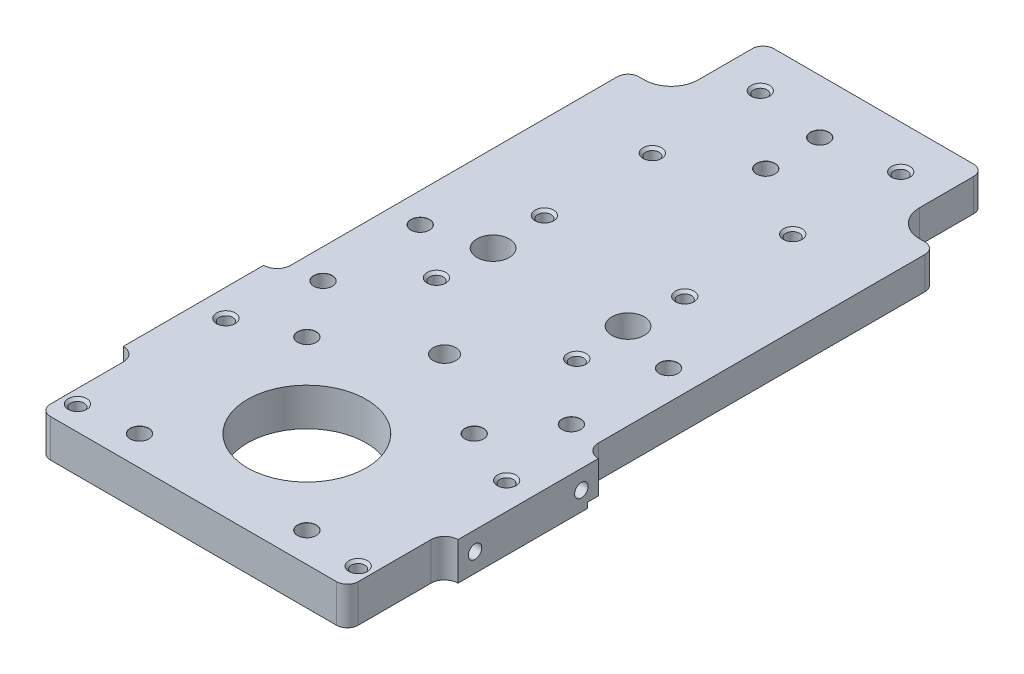
SolidWorks part; units mm, degrees
ref_plane "Top" through (0, 0, 0) normal (0, 0, 1) x (1, 0, 0)
ref_plane "Front" through (0, 0, 0) normal (0, 1, 0) x (1, 0, 0)
ref_plane "Right" through (0, 0, 0) normal (1, 0, 0) x (0, 0, -1)
ref_plane "Left Plane" through (-31, 0, 0) normal (1, 0, 0) x (0, 0, -1)
sketch "Plate Main Sketch" plane through (-158.0855, 0, 24.6791) normal (0, 1, 0) x (-1, 0, 0)
  line L1 (-178.5855, -24.6791) -> (-137.5855, -24.6791)
  line L2 (-127.0855, 57.3209) -> (-127.0855, 83.3209)
  line L3 (-129.5855, 101.3209) -> (-186.5855, 101.3209)
  line L4 (-129.5855, 101.3209) -> (-129.5855, 85.8209)
  line L5 (-158.0855, 101.3209) -> (-158.0855, -24.6791) construction
  line L6 (-178.5855, -12.6791) -> (-178.5855, -24.6791)
  line L7 (-129.5855, 54.8209) -> (-129.5855, -7.6791)
  line L8 (-129.5855, -7.6791) -> (-132.5855, -7.6791)
  line L9 (-137.5855, -12.6791) -> (-137.5855, -24.6791)
  line L10 (-186.5855, -7.6791) -> (-183.5855, -7.6791)
  line L11 (-186.5855, 54.8209) -> (-186.5855, -7.6791)
  line L12 (-189.0855, 57.3209) -> (-189.0855, 83.3209)
  line L13 (-186.5855, 101.3209) -> (-186.5855, 85.8209)
  arc A0 (-129.5855, 85.8209) -> (-127.0855, 83.3209) centre (-127.0855, 85.8209) ccw
  arc A1 (-129.5855, 54.8209) -> (-127.0855, 57.3209) centre (-127.0855, 54.8209) cw
  arc A2 (-132.5855, -7.6791) -> (-137.5855, -12.6791) centre (-132.5855, -12.6791) ccw
  arc A3 (-183.5855, -7.6791) -> (-178.5855, -12.6791) centre (-183.5855, -12.6791) cw
  arc A4 (-186.5855, 54.8209) -> (-189.0855, 57.3209) centre (-189.0855, 54.8209) ccw
  arc A5 (-186.5855, 85.8209) -> (-189.0855, 83.3209) centre (-189.0855, 85.8209) cw
  circle A18 centre (-158.0855, 80.3209) radius 11
  circle A20 centre (-145.5855, 33.3209) radius 3
  circle A21 centre (-170.5855, 33.3209) radius 3
  dimension "D2" = 5
  dimension "D8" = 22
  dimension "D9" = 6
  dimension "D1" = 2.5
  dimension "D3" = 62
  dimension "D4" = 126
  dimension "D5" = 18
  dimension "D6" = 44
  dimension "D15" = 21
  dimension "D17" = 8
  dimension "D7" = 109
  dimension "D10" = 58
  dimension "D11" = 16
extrude "Extrude Plate Main" add sketch "Plate Main Sketch" along normal blind 7
fillet "Corner Fillets" radius 2 6 edges at (-28.5, 3.5, 126) (-28.5, 3.5, 17) (-20.5, 3.5, 0) (20.5, 3.5, 0) (28.5, 3.5, 17) (28.5, 3.5, 126)
sketch "Reccess Sketch" plane through (0, 0, 0) normal (0, 1, 0) x (1, 0, 0)
  line L0 (-8.25, 0) -> (-8.25, -81)
  line L1 (-11.25, -84) -> (-31, -84)
  line L2 (-31, -84) -> (-31, 0)
  line L3 (-31, 0) -> (-8.25, 0)
  line L4 (0, 0) -> (0, -84) construction
  line L5 (31, 0) -> (8.25, 0)
  line L6 (8.25, 0) -> (8.25, -81)
  line L7 (31, -84) -> (31, 0)
  line L8 (11.25, -84) -> (31, -84)
  arc A0 (-8.25, -81) -> (-11.25, -84) centre (-11.25, -81) cw
  arc A1 (8.25, -81) -> (11.25, -84) centre (11.25, -81) ccw
  point P7 (-8.25, -84)
  dimension "D4" = 3
  dimension "D1" = 84
  dimension "D2" = 31
  dimension "D3" = 22.75
hole_wizard "M3x0.5 Tapped Holes" positions "Sketch12" profile "Sketch13" tap size "M3x0.5" standard "ANSI Metric" end condition through all
sketch "Sketch12" plane through (0, 0, 0) normal (0, -1, 0) x (-1, 0, 0)
  line L0 (-13, -8) -> (-13, -68) construction
  line L2 (13, -68) -> (13, -8) construction
  line L4 (26, -121.5) -> (-26, -121.5) construction
  line L5 (-26, -121.5) -> (-26, -94) construction
  line L6 (-26, -94) -> (26, -94) construction
  line L7 (26, -94) -> (26, -121.5) construction
  line L11 (31, -126) -> (-31, -126) construction
  line L12 (31, -126) -> (31, 0) construction
  line L13 (31, 0) -> (-31, 0) construction
  line L14 (-31, -126) -> (-31, 0) construction
  line L15 (0, 0) -> (0, -126) construction
  line L16 (31, -63) -> (-31, -63) construction
  point P0 (-26, -121.5)
  point P2 (-26, -94)
  point P4 (26, -94)
  point P8 (13, -68)
  point P10 (13, -48)
  point P12 (13, -28)
  point P14 (13, -8)
  point P16 (-13, -8)
  point P18 (-13, -28)
  point P20 (-13, -48)
  point P22 (-13, -68)
  point P477 (26, -121.5)
  dimension "D1" = 126
  dimension "D2" = 62
  dimension "D3" = 118
  dimension "D4" = 98
  dimension "D5" = 78
  dimension "D6" = 58
  dimension "D7" = 18
  dimension "D8" = 18
  dimension "D9" = 5
  dimension "D10" = 5
  dimension "D11" = 4.5
  dimension "D12" = 32
sketch "Sketch13" plane through (26, 0, 121.5) normal (1, 0, 0) x (0, 0, -1)
  line L0 (0, 0) -> (0, 7)
  line L1 (0, 7) -> (1.725, 7)
  line L2 (1.25, 6.525) -> (1.25, 0)
  line L5 (1.25, 0) -> (0, 0)
  line L7 (1.725, 7) -> (1.25, 6.525)
  line L8 (-1.725, 7) -> (-1.25, 6.525) construction
  line L11 (0, -6.35) -> (0, 107.95) construction
  dimension "Thru Tap Drill Dia." = 2.5
  dimension "Thru Tap Drill Depth" = 7
  dimension "Far C'Sink Dia." = 3.45
  dimension "Far C'Sink Angle" = 90
cosmetic thread "Hole Thread54" parameters "D2"=3
cosmetic thread "Hole Thread55" parameters "D2"=3
cosmetic thread "Hole Thread56" parameters "D2"=3
cosmetic thread "Hole Thread57" parameters "D2"=3
cosmetic thread "Hole Thread58" parameters "D2"=3
cosmetic thread "Hole Thread59" parameters "D2"=3
cosmetic thread "Hole Thread60" parameters "D2"=3
cosmetic thread "Hole Thread61" parameters "D2"=3
cosmetic thread "Hole Thread62" parameters "D2"=3
cosmetic thread "Hole Thread63" parameters "D2"=3
cosmetic thread "Hole Thread64" parameters "D2"=3
cosmetic thread "Hole Thread65" parameters "D2"=3
hole_wizard "M3 Counter Bores" positions "Sketch4" profile "Sketch5" counterbore size "M3" standard "ANSI Metric" end condition through all
sketch "Sketch4" plane through (0, 0, 0) normal (0, -1, 0) x (-1, 0, 0)
  line L0 (31, -126) -> (-31, -126) construction
  line L1 (-31, -126) -> (-31, 0) construction
  line L2 (-31, 0) -> (31, 0) construction
  line L3 (31, 0) -> (31, -126) construction
  line L5 (15.5, -120.5) -> (-15.5, -120.5) construction
  line L6 (-15.5, -120.5) -> (-15.5, -89.5) construction
  line L7 (-15.5, -89.5) -> (15.5, -89.5) construction
  line L8 (15.5, -89.5) -> (15.5, -120.5) construction
  line L10 (0, -126) -> (0, 0) construction
  point P0 (15.5, -120.5)
  point P3 (-15.5, -120.5)
  point P6 (-15.5, -89.5)
  point P9 (15.5, -89.5)
  point P12 (23, -79)
  point P15 (-23, -79)
  point P18 (-23, -61)
  point P21 (23, -61)
  point P24 (0, -20)
  point P27 (0, -10)
  point P42 (0, 0)
  point P65 (0, -120.5)
  dimension "D1" = 126
  dimension "D2" = 62
  dimension "D3" = 31
  dimension "D4" = 31
  dimension "D5" = 5.5
  dimension "D6" = 47
  dimension "D7" = 65
  dimension "D8" = 106
  dimension "D9" = 116
  dimension "D10" = 8
  dimension "D11" = 8
sketch "Sketch5" plane through (-15.5, 0, 120.5) normal (1, 0, 0) x (0, 0, -1)
  line L0 (0, 0) -> (0, 7)
  line L1 (1.7, 6.975) -> (1.725, 7)
  line L2 (1.7, 6.975) -> (1.7, 4.5)
  line L3 (1.7, 4.5) -> (3, 4.5)
  line L4 (3, 4.5) -> (3, 0)
  line L5 (3, 0) -> (0, 0)
  line L11 (0, -6.35) -> (0, 107.95) construction
  line L12 (1.725, 7) -> (0, 7)
  line L13 (-1.7, 6.975) -> (-1.725, 7) construction
  dimension "Thru Hole Dia." = 3.4
  dimension "Thru Hole Depth" = 7
  dimension "C'Bore Dia." = 6
  dimension "C'Bore Depth" = 4.5
  dimension "Far C'Sink Dia." = 3.45
  dimension "Far C'Sink Angle" = 90
hole_wizard "M5x0.8 Tapped Hole1" positions "Sketch14" profile "Sketch15" tap size "M5x0.8" standard "ANSI Metric" end condition through all
sketch "Sketch14" plane through (0, 0, 0) normal (0, -1, 0) x (-1, 0, 0)
  point P0 (0, -79.5)
  dimension "D1" = 79.5
sketch "Sketch15" plane through (0, 0, 79.5) normal (1, 0, 0) x (0, 0, -1)
  line L0 (0, 0) -> (0, 7)
  line L1 (0, 7) -> (2.1, 7)
  line L2 (2.1, 7) -> (2.1, 0)
  line L5 (2.1, 0) -> (0, 0)
  line L11 (0, -6.35) -> (0, 107.95) construction
  dimension "Thru Tap Drill Dia." = 4.2
  dimension "Thru Tap Drill Depth" = 7
cosmetic thread "Hole Thread66" parameters "D2"=5
extrude "Cut Recess" cut sketch "Reccess Sketch" along normal blind 1
hole_wizard "Left Z-Axis Sensors M3x0.5 Tapped Holes" positions "Sketch16" profile "Sketch17" tap size "M3x0.5" standard "ANSI Metric"
sketch "Sketch16" plane through (-31, 0, 0) normal (1, 0, 0) x (0, 0, -1)
  line L0 (0, 0) -> (-126, 0) construction
  line L2 (-108, 0) -> (-108, 7) construction
  line L4 (-82, 0) -> (-82, 7) construction
  line L6 (-108, 7) -> (-82, 7) construction
  line L8 (-108, 3.5) -> (-82, 3.5) construction
  line L10 (-95, 3.5) -> (-95, 0) construction
  point P0 (-85.15, 3.5)
  point P2 (-104.85, 3.5)
  dimension "D1" = 126
  dimension "D2" = 7
  dimension "D3" = 18
  dimension "D4" = 44
  dimension "D5" = 9.85
  dimension "D6" = 9.85
sketch "Sketch17" plane through (-31, 3.5, 85.15) normal (0, 1, 0) x (0, 0, 1)
  line L0 (0, 0) -> (0, 10.7511)
  line L1 (0, 10.7511) -> (1.25, 10)
  line L2 (1.25, 10) -> (1.25, 0)
  line L5 (1.25, 0) -> (0, 0)
  line L10 (0, 10.7511) -> (-1.25, 10) construction
  line L11 (0, -6.35) -> (0, 107.95) construction
  dimension "Tap Drill Dia." = 2.5
  dimension "Tap Drill Depth" = 10
  dimension "Drill Angle" = 118
cosmetic thread "Hole Thread67" parameters "D1"=7, "D2"=3
cosmetic thread "Hole Thread68" parameters "D1"=7, "D2"=3
mirror "Right Z-Axis Sensor Holes Mirror" about plane through (0, 0, 0) normal (1, 0, 0) of "Left Z-Axis Sensors M3x0.5 Tapped Holes"
cosmetic thread "Hole Thread69" parameters "D1"=7, "D2"=3
cosmetic thread "Hole Thread70" parameters "D1"=7, "D2"=3
equation "\"M2 Close Fit Hole\"= 2.2"
equation "\"M2.5 Close Fit Hole\"= 2.7"
equation "\"M3 Close Fit Hole\"= 3.2"
equation "\"M4 Close Fit Hole\"= 4.3"
equation "\"M5 Close Fit Hole\"= 5.3"
equation "\"M6 Close Fit Hole\"= 6.3"
equation "\"M7 Close Fit Hole\"= 7.4"
equation "\"M8 Close Fit Hole\"= 8.4"
equation "\"M2 Tap Hole 75%\"= 1.6"
equation "\"M3 Tap Hole 75%\"= 2.5"
equation "\"M4 Tap Hole 75%\"= 3.3"
equation "\"M5 Tap Hole 75%\"= 4.2"
equation "\"M6 Tap Hole 75%\"= 5"
equation "\"M7 Tap Hole 75%\"= 6"
equation "\"M8 Tap Hole 75%\"= 6.8"
equation "\"Bracket Width\"= 62mm"
equation "\"D3@Plate Main Sketch\"=\"Bracket Width\""
equation "\"Bracket Height\"= 126mm"
equation "\"D4@Plate Main Sketch\"=\"Bracket Height\""
equation "\"D1@Sketch4\"=\"Bracket Height\""
equation "\"D2@Sketch4\"=\"Bracket Width\""
equation "\"D1@Sketch12\"=\"Bracket Height\""
equation "\"D2@Sketch12\"=\"Bracket Width\""
equation "\"D2@Reccess Sketch\" = 0.5 * \"Bracket Width\""
equation "\"D1@Left Plane\" = \"Bracket Width\" / 2"
equation "\"D1@Sketch16\"=\"Bracket Height\""
equation "\"D2@Sketch16\"=\"Bracket Thickness\""
equation "\"Bracket Thickness\"= 7mm"
equation "\"Thickness@Extrude Plate Main\"=\"Bracket Thickness\""
